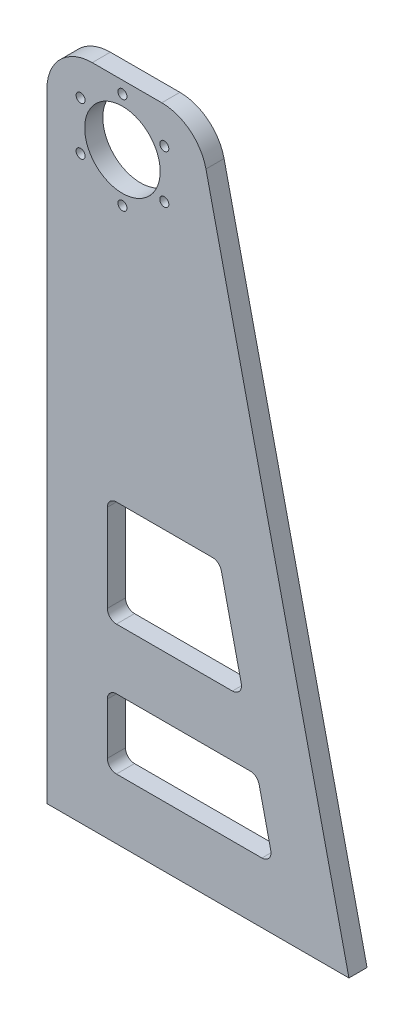
SolidWorks part; units mm, degrees
ref_plane "Plano frontal" through (0, 0, 0) normal (0, 0, 1) x (1, 0, 0)
ref_plane "Plano superior" through (0, 0, 0) normal (0, 1, 0) x (1, 0, 0)
ref_plane "Plano direito" through (0, 0, 0) normal (1, 0, 0) x (0, 0, -1)
sketch "Esboço1" plane through (0, 0, 0) normal (0, 0, 1) x (1, 0, 0)
  line L0 (0, 0) -> (0, 220)
  line L2 (100, 0) -> (0, 0)
  line L3 (0, 220) -> (50, 220)
  line L4 (50, 220) -> (100, 0)
  line L5 (10, 75.5) -> (10, 15) construction
  line L6 (25, 220) -> (25, 180) construction
  line L7 (10, 15) -> (85.7122, 15) construction
  line L8 (85.7122, 15) -> (71.9622, 75.5) construction
  line L9 (71.9622, 75.5) -> (10, 75.5) construction
  line L10 (20, 95) -> (20, 66)
  line L11 (23, 63) -> (61.4135, 63)
  line L12 (64.3389, 66.6649) -> (57.748, 95.6649)
  line L13 (54.8226, 98) -> (23, 98)
  line L14 (20, 40) -> (20, 23)
  line L15 (23, 20) -> (71.1862, 20)
  line L16 (74.1116, 23.6649) -> (70.248, 40.6649)
  line L17 (23, 43) -> (67.3226, 43)
  circle A0 centre (25, 200) radius 12.5
  circle A1 centre (25, 200) radius 16 construction
  circle A2 centre (25, 216) radius 1.5
  arc A8 (70.248, 40.6649) -> (67.3226, 43) centre (67.3226, 40) ccw
  arc A9 (71.1862, 20) -> (74.1116, 23.6649) centre (71.1862, 23) ccw
  arc A10 (20, 23) -> (23, 20) centre (23, 23) ccw
  arc A11 (20, 40) -> (23, 43) centre (23, 40) cw
  arc A12 (57.748, 95.6649) -> (54.8226, 98) centre (54.8226, 95) ccw
  arc A13 (61.4135, 63) -> (64.3389, 66.6649) centre (61.4135, 66) ccw
  arc A14 (20, 66) -> (23, 63) centre (23, 66) ccw
  arc A15 (20, 95) -> (23, 98) centre (23, 95) cw
  circle A16 centre (38.8564, 208) radius 1.5
  circle A17 centre (38.8564, 192) radius 1.5
  circle A18 centre (25, 184) radius 1.5
  circle A19 centre (11.1436, 192) radius 1.5
  circle A20 centre (11.1436, 208) radius 1.5
  point P26 (22.5, 105)
  point P49 (20, 63)
  point P55 (25, 175)
  point P56 (25, 200)
  dimension "D3" = 20
  dimension "D4" = 25
  dimension "D6" = 32
  dimension "D7" = 3
  dimension "D21" = 3
  dimension "D1" = 220
  dimension "D2" = 100
  dimension "D5" = 50
  dimension "D9" = 25
  dimension "D10" = 6
  dimension "D11" = 20
  dimension "D12" = 20
  dimension "D13" = 15
  dimension "D14" = 20
  dimension "D18" = 10
  dimension "D20" = 20
  dimension "D22" = 23
  dimension "D8" = 35
extrude "Ressalto-extrusão2" add sketch "Esboço1" along normal blind 6
fillet "Filete1" radius 15 2 edges at (0, 220, 3) (50, 220, 3)
